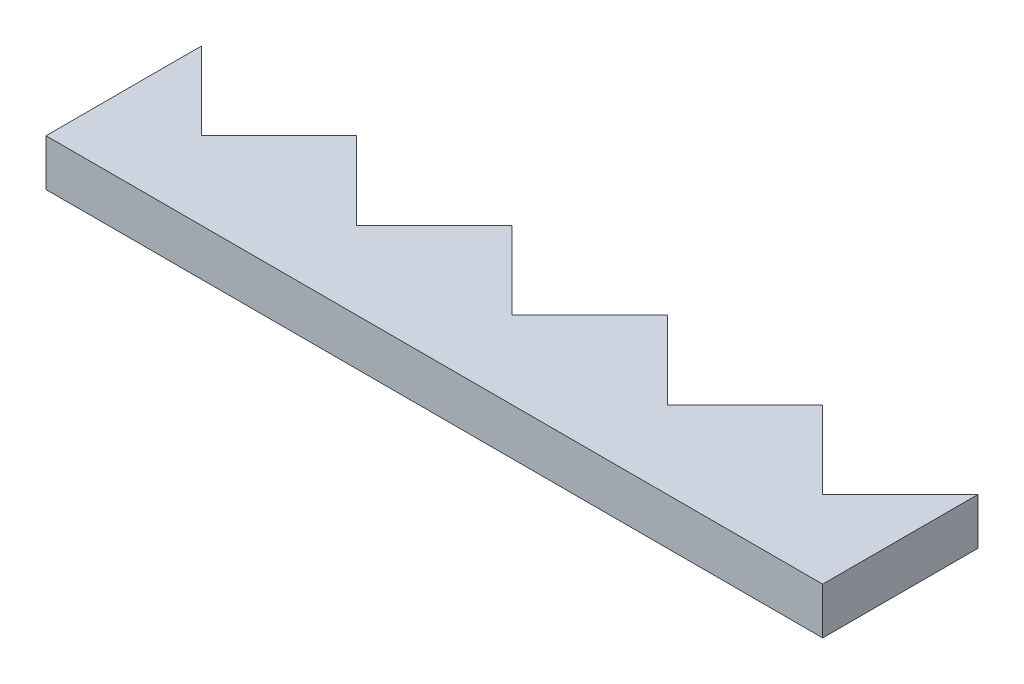
SolidWorks part; units mm, degrees
material "Custom Plastic"
ref_plane "Front Plane" through (0, 0, 0) normal (0, 0, 1) x (1, 0, 0)
ref_plane "Top Plane" through (0, 0, 0) normal (0, 1, 0) x (1, 0, 0)
ref_plane "Right Plane" through (0, 0, 0) normal (1, 0, 0) x (0, 0, -1)
sketch "Sketch1" plane through (0, 0.3303, 0) normal (0, 1, 0) x (1, 0, 0)
  line L0 (0, 0) -> (0, 10)
  line L1 (0, 10) -> (5, 5)
  line L2 (5, 5) -> (10, 10)
  line L4 (10, 10) -> (15, 5)
  line L5 (15, 5) -> (20, 10)
  line L6 (20, 10) -> (25, 5)
  line L7 (25, 5) -> (30, 10)
  line L8 (30, 10) -> (35, 5)
  line L9 (35, 5) -> (40, 10)
  line L10 (40, 10) -> (45, 5)
  line L11 (45, 5) -> (50, 10)
  line L16 (0, 0) -> (50, 0)
  line L17 (50, 0) -> (50, 10)
  dimension "D1" = 10
  dimension "D2" = 10
  dimension "D3" = 5
  dimension "D4" = 5
extrude "Boss-Extrude1" add sketch "Sketch1" along normal blind 3
